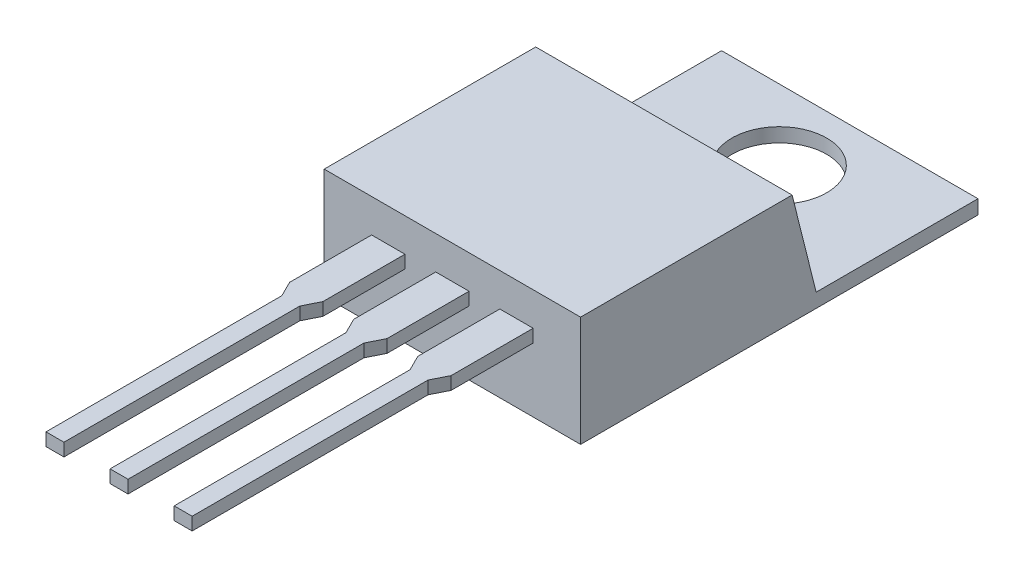
SolidWorks part; units mm, degrees
ref_plane "Front Plane" through (0, 0, 0) normal (0, 0, 1) x (1, 0, 0)
ref_plane "Top Plane" through (0, 0, 0) normal (0, 1, 0) x (1, 0, 0)
ref_plane "Right Plane" through (0, 0, 0) normal (1, 0, 0) x (0, 0, -1)
sketch "Sketch1" plane through (0, 0, 0) normal (0, 1, 0) x (1, 0, 0)
  line L0 (5, 15.5) -> (5, 0) construction
  line L1 (0, 0) -> (10, 0)
  line L2 (0, 0) -> (0, 15.5)
  line L3 (0, 15.5) -> (10, 15.5)
  line L4 (10, 0) -> (10, 15.5)
  circle A0 centre (5, 12.75) radius 1.85
  dimension "D4" = 3.7
  dimension "D1" = 2.75
  dimension "D2" = 10
  dimension "D3" = 15.5
extrude "Boss-Extrude1" add sketch "Sketch1" along normal blind 0.55
sketch "Sketch2" plane through (0, 0.55, 0) normal (0, 1, 0) x (1, 0, 0)
  line L0 (10, 0) -> (10, 15.5) construction
  line L1 (0, 0) -> (10, 0)
  line L2 (0, 0) -> (0, 9.25)
  line L3 (0, 9.25) -> (10, 9.25)
  line L4 (10, 0) -> (10, 9.25)
  line L5 (10, 15.5) -> (0, 15.5) construction
  dimension "D1" = 6.25
extrude "Boss-Extrude2" add sketch "Sketch2" along normal blind 3.75
chamfer "Chamfer1" distance 4 distance2 1 1 edges at (5, 4.3, -9.25) first distance on face at (5, 2.425, -9.25)
sketch "Sketch3" plane through (0, 0, 0) normal (0, 0, 1) x (1, 0, 0)
  line L0 (5, 4.3) -> (5, 0) construction
  line L1 (1.85, 3) -> (3.15, 3)
  line L2 (1.85, 3) -> (1.85, 2.5)
  line L3 (1.85, 2.5) -> (3.15, 2.5)
  line L4 (3.15, 3) -> (3.15, 2.5)
  line L5 (4.35, 3) -> (5.65, 3)
  line L6 (4.35, 3) -> (4.35, 2.5)
  line L7 (4.35, 2.5) -> (5.65, 2.5)
  line L8 (5.65, 3) -> (5.65, 2.5)
  line L9 (6.85, 3) -> (8.15, 3)
  line L10 (6.85, 3) -> (6.85, 2.5)
  line L11 (6.85, 2.5) -> (8.15, 2.5)
  line L12 (8.15, 3) -> (8.15, 2.5)
  line L13 (0, 4.3) -> (10, 4.3) construction
  line L14 (0, 0) -> (10, 0) construction
  point P18 (5, 3)
  dimension "D1" = 2.5
  dimension "D2" = 0.5
  dimension "D3" = 1.3
  dimension "D4" = 1.2
  dimension "D5" = 1.2
extrude "Boss-Extrude3" add sketch "Sketch3" along normal blind 13
sketch "Sketch4" plane through (0, 3, 0) normal (0, 1, 0) x (1, 0, 0)
  line L0 (1.85, -3.2) -> (2.15, -3.8)
  line L1 (1.85, -13) -> (1.85, 0) construction
  line L2 (2.15, -3.8) -> (2.15, -13)
  line L3 (3.15, -13) -> (1.85, -13) construction
  line L4 (2.15, -13) -> (1.85, -13)
  line L5 (1.85, -13) -> (1.85, -3.2)
  line L6 (4.35, -3.2) -> (4.65, -3.8)
  line L7 (4.65, -3.8) -> (4.65, -13)
  line L8 (4.65, -13) -> (4.35, -13)
  line L9 (4.35, -13) -> (4.35, -3.2)
  line L10 (6.85, -3.2) -> (7.15, -3.8)
  line L11 (7.15, -3.8) -> (7.15, -13)
  line L12 (7.15, -13) -> (6.85, -13)
  line L13 (6.85, -13) -> (6.85, -3.2)
  line L14 (3.15, 0) -> (1.85, 0) construction
  line L15 (3.15, -3.2) -> (2.85, -3.8)
  line L16 (3.15, -13) -> (3.15, 0) construction
  line L17 (2.85, -3.8) -> (2.85, -13)
  line L18 (2.85, -13) -> (3.15, -13)
  line L19 (3.15, -13) -> (3.15, -3.2)
  line L20 (5.65, -3.2) -> (5.35, -3.8)
  line L21 (5.35, -3.8) -> (5.35, -13)
  line L22 (5.35, -13) -> (5.65, -13)
  line L23 (5.65, -13) -> (5.65, -3.2)
  line L24 (8.15, -3.2) -> (7.85, -3.8)
  line L25 (7.85, -3.8) -> (7.85, -13)
  line L26 (7.85, -13) -> (8.15, -13)
  line L27 (8.15, -13) -> (8.15, -3.2)
  dimension "D1" = 3.2
  dimension "D2" = 0.7
  dimension "D3" = 0.6
extrude "Cut-Extrude1" cut sketch "Sketch4" against normal through all
